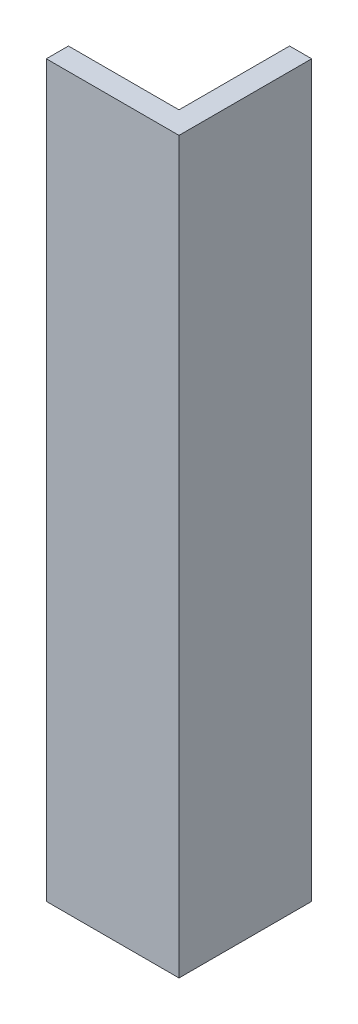
SolidWorks part; units mm, degrees
ref_plane "Front Plane" through (0, 0, 0) normal (0, 0, 1) x (1, 0, 0)
ref_plane "Top Plane" through (0, 0, 0) normal (0, 1, 0) x (1, 0, 0)
ref_plane "Right Plane" through (0, 0, 0) normal (1, 0, 0) x (0, 0, -1)
sketch "Sketch1" plane through (0, 0, 0) normal (0, 1, 0) x (1, 0, 0)
  line L1 (0, 0) -> (15.24, 0)
  line L2 (0, 0) -> (0, 2.54)
  line L3 (0, 2.54) -> (12.7, 2.54)
  line L4 (15.24, 0) -> (15.24, 2.54)
  line L5 (15.24, 0) -> (12.9637, 0)
  line L6 (15.24, 0) -> (15.24, 15.24)
  line L7 (15.24, 15.24) -> (12.7, 15.24)
  line L8 (12.7, 2.54) -> (12.7, 15.24)
  dimension "D1" = 12.7
  dimension "D2" = 12.7
  dimension "D3" = 2.54
  dimension "D4" = 2.54
extrude "Boss-Extrude1" add sketch "Sketch1" along normal blind 83.82 contours L8 L3 L2 L1 L4 L6 L7 region at (0.2155, 0, -1.27)
